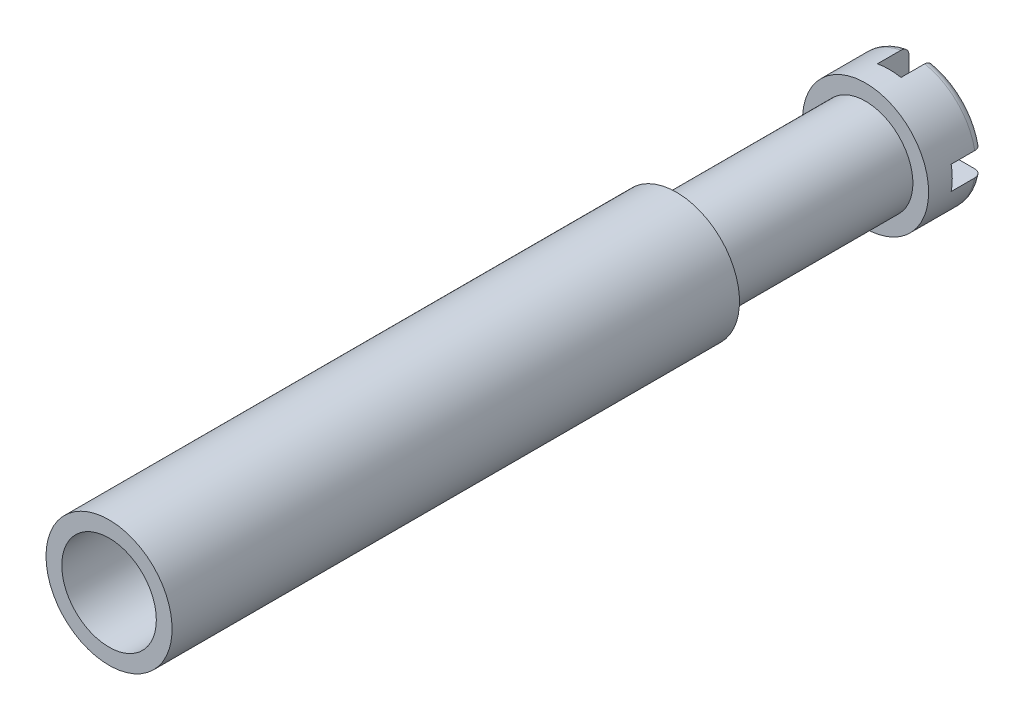
SolidWorks part; units mm, degrees
material "Alloy Steel"
ref_plane "Front Plane" through (0, 0, 0) normal (0, 0, 1) x (1, 0, 0)
ref_plane "Top Plane" through (0, 0, 0) normal (0, 1, 0) x (1, 0, 0)
ref_plane "Right Plane" through (0, 0, 0) normal (1, 0, 0) x (0, 0, -1)
sketch "Sketch1" plane through (0, 0, 0) normal (0, 0, 1) x (1, 0, 0)
  circle A0 centre (0, 0) radius 3
  circle A1 centre (0, 0) radius 4
  dimension "D1" = 8
  dimension "D2" = 6
extrude "Boss-Extrude1" add sketch "Sketch1" along normal blind 12 contours A0
extrude "Boss-Extrude2" add sketch "Sketch1<4>" against normal blind 3.5 contours A0 | A1 A0 region at (0, 0, 0) region at (-3.8869, 0, 0)
sketch "Sketch1<4>" plane through (0, 0, 0) normal (0, 0, 1) x (1, 0, 0) same geometry as "Sketch1"
sketch "Sketch2" plane through (0, 0, -3.5) normal (0, 0, -1) x (-1, 0, 0)
  line L0 (0, 0) -> (-4, 0) construction
  line L1 (0, 0) -> (0, 4) construction
  line L4 (-0.75, 3.9291) -> (-0.75, 0.75)
  line L6 (0.75, 3.9291) -> (0.75, 0.75)
  line L9 (-3.9291, 0.75) -> (-0.75, 0.75)
  line L11 (-3.9291, -0.75) -> (-0.75, -0.75)
  line L17 (0.75, 0.75) -> (3.9291, 0.75)
  line L20 (-0.75, -0.75) -> (-0.75, -3.9291)
  line L21 (0.75, -0.75) -> (0.75, -3.9291)
  line L22 (0.75, -0.75) -> (3.9291, -0.75)
  circle A0 centre (0, 0) radius 4 construction
  arc A1 (-3.9291, 0.75) -> (-3.9291, -0.75) centre (0, 0) ccw
  arc A2 (0.75, 3.9291) -> (-0.75, 3.9291) centre (0, 0) ccw
  arc A3 (3.9291, -0.75) -> (3.9291, 0.75) centre (0, 0) ccw
  arc A4 (-0.75, -3.9291) -> (0.75, -3.9291) centre (0, 0) ccw
  circle A5 centre (0, 0) radius 1.25
  circle M17 centre (0, 0) radius 4
  dimension "D7" = 2.5
  dimension "D1" = 1.5
  dimension "D2" = 1.5
  dimension "D3" = 0.75
  dimension "D4" = 0.75
  dimension "D5" = 0.75
  dimension "D6" = 0.75
extrude "Cut-Extrude1" cut sketch "Sketch2" against normal blind 2 contours A5 L6 L4 M17 | A5 L9 L11 M17 | A5 L22 L17 M17 | A5 L20 L21 M17 | L6 A5 L4 L9 L11 L20 L21 L22 L17 | L4 A5 L9 | L17 A5 L6 | L21 A5 L22 | L11 A5 L20 region at (0, 2.5725, -3.5) region at (0, 0, -3.5) region at (0.8373, 0.8373, -3.5) region at (2.5725, 0, -3.5) region at (-0.8373, 0.8373, -3.5) region at (-2.5725, 0, -3.5) region at (0.8373, -0.8373, -3.5) region at (0, -2.5725, -3.5) region at (-0.8373, -0.8373, -3.5)
fillet "Fillet1" radius 0.5 4 edges at (2.8284, 2.8284, -3.5) (2.8284, -2.8284, -3.5) (-2.8284, -2.8284, -3.5) (-2.8284, 2.8284, -3.5)
extrude "Cut-Extrude2" cut sketch "Sketch2<3>" against normal blind 1 draft 20 from surface contours A5 starting at face at (0, 0, -1.5)
sketch "Sketch2<3>" plane through (0, 0, -3.5) normal (0, 0, -1) x (-1, 0, 0) same geometry as "Sketch2"
fillet "Fillet2" radius 0.5 1 edges at (-0.886, 0, -0.5)
extrude "Boss-Extrude3" add sketch "Sketch1<5>" along normal blind 36 from surface contours A1 starting at face at (3, 0, 12)
sketch "Sketch1<5>" plane through (0, 0, 0) normal (0, 0, 1) x (1, 0, 0) same geometry as "Sketch1"
sketch "Sketch9" plane through (0, 0, 48) normal (0, 0, 1) x (1, 0, 0)
  circle A0 centre (0, 0) radius 3
  dimension "D1" = 6
extrude "Cut-Extrude3" cut sketch "Sketch9" against normal blind 20
